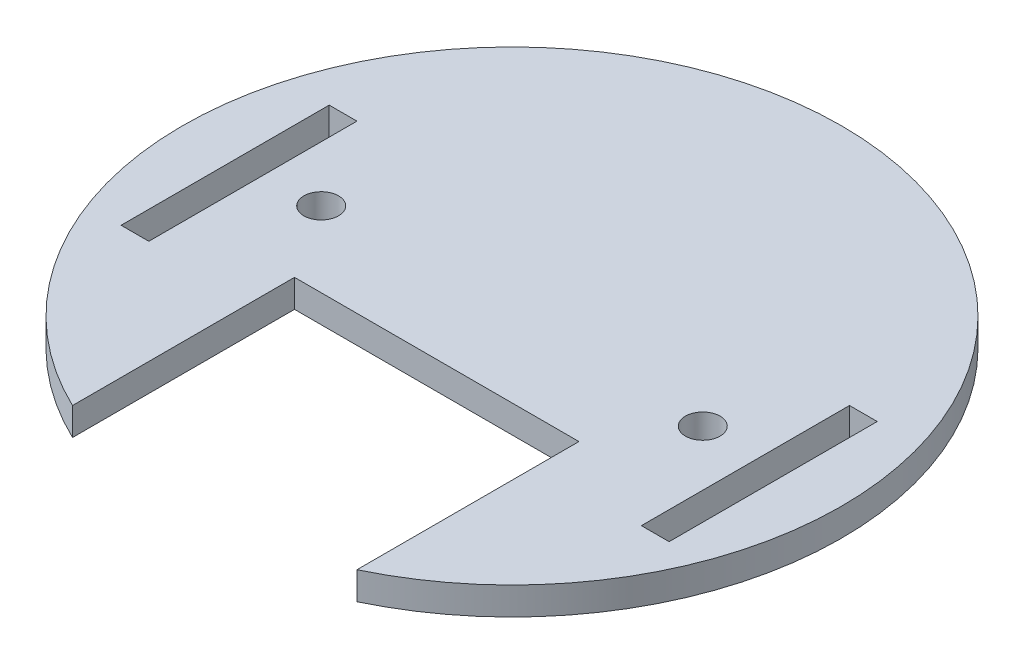
SolidWorks part; units mm, degrees
ref_plane "Front Plane" through (0, 0, 0) normal (0, 0, 1) x (1, 0, 0)
ref_plane "Top Plane" through (0, 0, 0) normal (0, 1, 0) x (1, 0, 0)
ref_plane "Right Plane" through (0, 0, 0) normal (1, 0, 0) x (0, 0, -1)
sketch "Sketch1" plane through (0, 0, 0) normal (0, 1, 0) x (1, 0, 0)
  line L0 (-47.5, 0) -> (47.5, 0) construction
  line L1 (0, 47.5) -> (0, -47.75) construction
  line L2 (-20.5, -42.8486) -> (-20.5, -10.8486)
  line L3 (-20.5, -10.8486) -> (20.5, -10.8486)
  line L4 (20.5, -10.8486) -> (20.5, -42.8486)
  line L5 (35.5, -16.8486) -> (39.5, -16.8486)
  line L6 (-35.5, -16.8486) -> (-39.5, -16.8486)
  line L7 (-35.5, -16.8486) -> (-35.5, 9.1514)
  line L8 (-35.5, 9.1514) -> (-35.5, 13.1514)
  line L9 (-39.5, -16.8486) -> (-39.5, 13.1514)
  line L10 (35.5, 9.1514) -> (35.5, 13.1514)
  line L11 (39.5, -16.8486) -> (39.5, 13.1514)
  line L12 (35.5, -16.8486) -> (35.5, 9.1514)
  line L13 (35.5, 13.1514) -> (39.5, 13.1514)
  line L14 (-39.5, 13.1514) -> (-35.5, 13.1514)
  arc A0 (20.5, -42.8486) -> (-20.5, -42.8486) centre (0, 0) ccw
  circle A1 centre (-27.5, 0) radius 2.5
  circle A2 centre (27.5, 0) radius 2.5
  dimension "D1" = 95
  dimension "D2" = 5
  dimension "D9" = 15
  dimension "D3" = 55
  dimension "D4" = 32
  dimension "D5" = 41
  dimension "D6" = 30
  dimension "D7" = 4
  dimension "D11" = 30
extrude "Boss-Extrude2" add sketch "Sketch1" along normal blind 4
